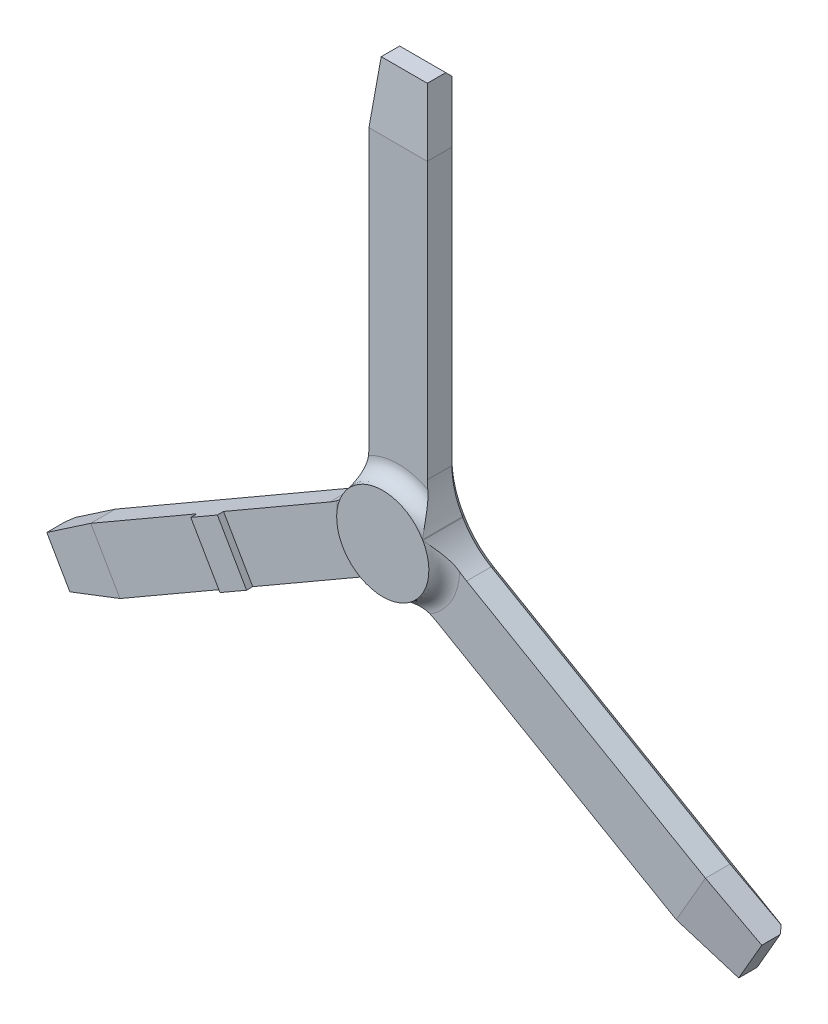
SolidWorks part; units mm, degrees
ref_plane "Front Plane" through (0, 0, 0) normal (0, 0, 1) x (1, 0, 0)
ref_plane "Top Plane" through (0, 0, 0) normal (0, 1, 0) x (1, 0, 0)
ref_plane "Right Plane" through (0, 0, 0) normal (1, 0, 0) x (0, 0, -1)
sketch "Sketch1" plane through (0, 0, 0) normal (0, 0, 1) x (1, 0, 0)
  line L0 (-1.9, 24) -> (1.9, 24) construction
  line L1 (0, 0) -> (0, 24) construction
  line L2 (-1.9, 24) -> (-1.9, 26)
  line L3 (-1.9, 26) -> (1.9, 26)
  line L4 (1.9, 26) -> (1.9, 24)
  line L5 (23.4667, -11.3546) -> (21.5667, -14.6454)
  line L6 (21.5667, -14.6454) -> (19.8346, -13.6454)
  line L7 (21.7346, -10.3546) -> (23.4667, -11.3546)
  line L8 (-21.5667, -14.6454) -> (-23.4667, -11.3546)
  line L9 (-23.4667, -11.3546) -> (-21.7346, -10.3546)
  line L10 (-19.8346, -13.6454) -> (-21.5667, -14.6454)
  line L11 (0, 0) -> (1.9, 24) construction
  line L12 (0, 0) -> (19.8346, -13.6454) construction
  line L13 (-1.9, 24) -> (-1.9, 1.097)
  line L14 (-1.9, 1.097) -> (-21.7346, -10.3546)
  line L15 (-19.8346, -13.6454) -> (0, -2.1939)
  line L16 (0, -2.1939) -> (19.8346, -13.6454)
  line L17 (21.7346, -10.3546) -> (1.9, 1.097)
  line L18 (1.9, 1.097) -> (1.9, 24)
  circle A0 centre (0, 0) radius 24 construction
  dimension "D1" = 48
  dimension "D2" = 3.8
  dimension "D3" = 2
  dimension "D4" = 120
  dimension "D5" = 24.0751
  dimension "D6" = 3
extrude "Boss-Extrude1" add sketch "Sketch1" along normal blind 2 contours L18 A0 L13 L14 L15 L16 L17 region at (0, 0, 0)
chamfer "Chamfer1" distance 4 distance2 0.4 3 edges at (22.5167, -13, 2) (-22.5167, -13, 2) (0, 26, 2) first distance on face at (0, 0, 2)
chamfer "Chamfer2" distance 0.4 distance2 4 3 edges at (23.4667, -11.3546, 0.8) (-1.9, 26, 0.8) (-21.5667, -14.6454, 0.8) first distance on face at (22.5167, -13, 0.8) first distance on face at (0, 26, 0.8) first distance on face at (-22.5167, -13, 0.8)
chamfer "Chamfer3" distance 4 distance2 0.4 3 edges at (1.9, 26, 0.8) (21.5667, -14.6454, 0.8) (-23.4667, -11.3546, 0.8) first distance on face at (1.9, 15.2388, 1.12) first distance on face at (12.2472, -9.2648, 1.12) first distance on face at (-14.1472, -5.9739, 1.12)
sketch "Sketch2" plane through (0, 0, 0) normal (0, 0, -1) x (-1, 0, 0)
  circle A0 centre (0, 0) radius 3
  dimension "D1" = 6
extrude "Boss-Extrude2" add sketch "Sketch2" against normal blind 3
fillet "Fillet1" radius 5 6 edges at (1.9, 2.3216, 1) (2.9606, 0.4846, 1) (1.0606, -2.8063, 1) (-1.0606, -2.8063, 1) (-2.9606, 0.4846, 1) (-1.9, 2.3216, 1)
fillet "Fillet2" radius 1 3 edges at (0, 3, 2) (2.5981, -1.5, 2) (-2.5981, -1.5, 2)
chamfer "Chamfer4" distance 0.4 angle 45 18 edges at (22.5167, -13, 0) (-22.5167, -13, 0) (0, 26, 0) (12.2293, -4.8667, 0) (3.4082, 0.4282, 0) (2.5981, 1.5, 0) (2.0749, 2.7374, 0) (1.9, 13.0242, 0) (-12.2293, -4.8667, 0) (-3.4082, 0.4282, 0) (-2.5981, 1.5, 0) (-2.0749, 2.7374, 0) (-1.9, 13.0242, 0) (10.3293, -8.1576, 0) (1.3332, -3.1657, 0) (0, -3, 0) (-1.3332, -3.1657, 0) (-10.3293, -8.1576, 0)
sketch "Sketch3" plane through (0, 0, 2) normal (0, 0, 1) x (1, 0, 0)
  line L0 (-12.2293, -4.8667) -> (-10.3293, -8.1576) construction
  line L1 (-4.4561, -0.3788) -> (-20.0026, -9.3546) construction
  line L2 (-2.5561, -3.6697) -> (-18.1026, -12.6454) construction
  line L3 (-13.0953, -5.3667) -> (-11.1953, -8.6576)
  line L7 (-13.0953, -5.3667) -> (-11.3633, -4.3667)
  line L8 (-11.1953, -8.6576) -> (-9.4633, -7.6576)
  line L9 (-11.3633, -4.3667) -> (-9.4633, -7.6576)
  line L10 (-13.0953, -5.3667) -> (-9.4633, -7.6576) construction
  line L11 (-11.1953, -8.6576) -> (-11.3633, -4.3667) construction
  point P13 (-11.2793, -6.5121)
  dimension "D1" = 2
extrude "Boss-Extrude3" add sketch "Sketch3" along normal blind 0.4
